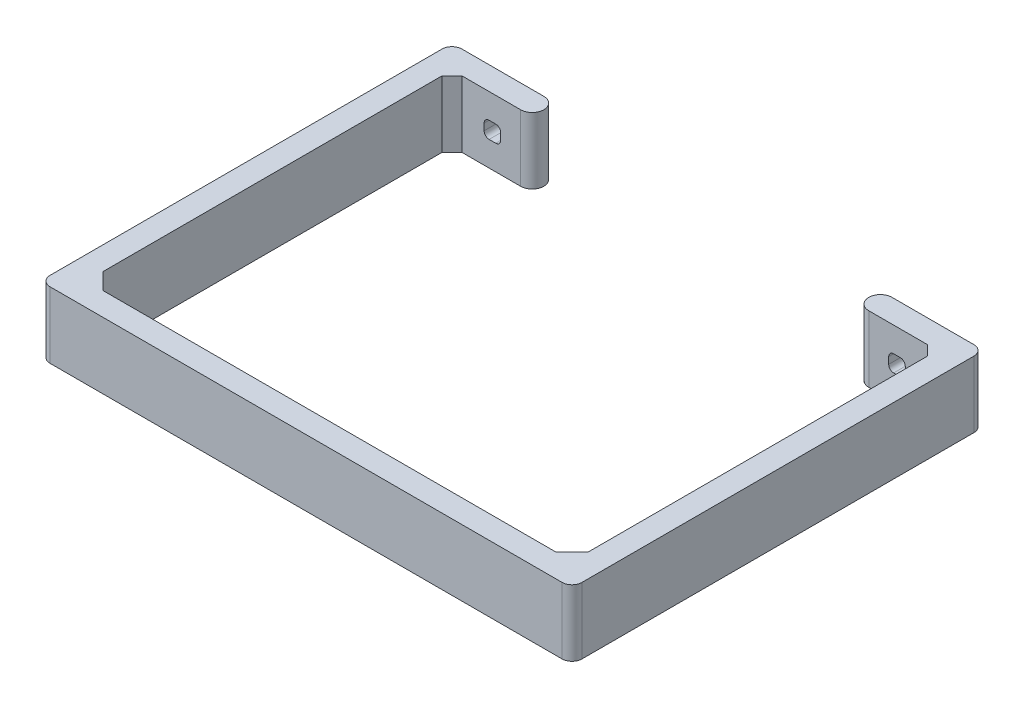
SolidWorks part; units mm, degrees
ref_plane "Plano frontal" through (0, 0, 0) normal (0, 0, 1) x (1, 0, 0)
ref_plane "Plano superior" through (0, 0, 0) normal (0, 1, 0) x (1, 0, 0)
ref_plane "Plano direito" through (0, 0, 0) normal (1, 0, 0) x (0, 0, -1)
sketch "Esboço1" plane through (0, 0, 0) normal (0, 1, 0) x (1, 0, 0)
  line L0 (-80.2, 62.1) -> (-80.2, -62.1)
  line L1 (-73.2, 55.1) -> (73.2, 55.1)
  line L2 (-73.2, 55.1) -> (-73.2, -55.1)
  line L3 (-73.2, -55.1) -> (73.2, -55.1)
  line L4 (73.2, 55.1) -> (73.2, -55.1)
  line L5 (-73.2, 55.1) -> (73.2, -55.1) construction
  line L6 (-73.2, -55.1) -> (73.2, 55.1) construction
  line L7 (-80.2, -62.1) -> (80.2, -62.1)
  line L8 (80.2, 62.1) -> (80.2, -62.1)
  line L9 (-80.2, 62.1) -> (80.2, 62.1)
  point P0 (0, 0)
  dimension "D1" = 110.2
  dimension "D2" = 146.4
  dimension "D3" = 7
extrude "Paredes" add sketch "Esboço1" along normal blind 20
chamfer "Chanfros Interno Frente" distance 5 angle 45 2 edges at (73.2, 10, 55.1) (-73.2, 10, 55.1)
fillet "Filete1" radius 3 1 edges at (-80.2, 10, 62.1) type face fillet first side face at (-80.2, 10, 0) second side face at (0, 10, 62.1)
fillet "Filete2" radius 3 1 edges at (80.2, 10, 62.1) type face fillet first side face at (80.2, 10, 0) second side face at (1.5, 10, 62.1)
sketch "Esboço2" plane through (0, 0, -62.1) normal (0, 0, -1) x (-1, 0, 0)
  line L0 (0, 24.9674) -> (0, -4.9674) construction
  line L1 (91.2754, 10) -> (-89.5946, 10) construction
  line L2 (-49, 25) -> (49, 25)
  line L3 (-49, 25) -> (-49, -5)
  line L4 (-49, -5) -> (49, -5)
  line L5 (49, 25) -> (49, -5)
  line L6 (-49, 25) -> (49, -5) construction
  line L7 (-49, -5) -> (49, 25) construction
  line L8 (58.5, 11) -> (58.5, 9)
  line L9 (-62, 12.5) -> (-60, 12.5)
  line L10 (-63.5, 11) -> (-63.5, 9)
  line L11 (-62, 7.5) -> (-60, 7.5)
  line L12 (-58.5, 11) -> (-58.5, 9)
  line L13 (-63.5, 12.5) -> (-58.5, 7.5) construction
  line L14 (-63.5, 7.5) -> (-58.5, 12.5) construction
  line L15 (62, 7.5) -> (60, 7.5)
  line L16 (63.5, 11) -> (63.5, 9)
  line L17 (62, 12.5) -> (60, 12.5)
  arc A0 (-62, 7.5) -> (-63.5, 9) centre (-62, 9) cw
  arc A1 (-60, 7.5) -> (-58.5, 9) centre (-60, 9) ccw
  arc A2 (-58.5, 11) -> (-60, 12.5) centre (-60, 11) ccw
  arc A3 (-62, 12.5) -> (-63.5, 11) centre (-62, 11) ccw
  arc A4 (58.5, 11) -> (60, 12.5) centre (60, 11) cw
  arc A5 (60, 7.5) -> (58.5, 9) centre (60, 9) cw
  arc A6 (62, 7.5) -> (63.5, 9) centre (62, 9) ccw
  arc A7 (62, 12.5) -> (63.5, 11) centre (62, 11) cw
  point P3 (0, 10)
  point P10 (-61, 10)
  dimension "D6" = 1.5
  dimension "D1" = 98
  dimension "D2" = 10
  dimension "D3" = 30
  dimension "D4" = 5
  dimension "D5" = 5
  dimension "D7" = 61
extrude "Corte-extrusão1" cut sketch "Esboço2" against normal blind 20
fillet "Filete3" 2 edges at (49, 10, -62.1) (49, 10, -55.1) type full round first side face at (61, 10, -62.1) second side face at (61, 10, -55.1) middle face at (49, 10, -58.6)
fillet "Filete4" 2 edges at (-49, 10, -55.1) (-49, 10, -62.1) type full round first side face at (-61, 10, -55.1) second side face at (-61, 10, -62.1) middle face at (-49, 10, -58.6)
fillet "Filete5" radius 3 1 edges at (-80.2, 10, -62.1) type face fillet first side face at (-80.2, 10, -1.5) second side face at (-61, 10, -62.1)
fillet "Filete6" radius 3 1 edges at (80.2, 10, -62.1) type face fillet first side face at (80.2, 10, -1.5) second side face at (61, 10, -62.1)
chamfer "Chanfro2" distance 3 angle 45 2 edges at (73.2, 10, -55.1) (-73.2, 10, -55.1)
